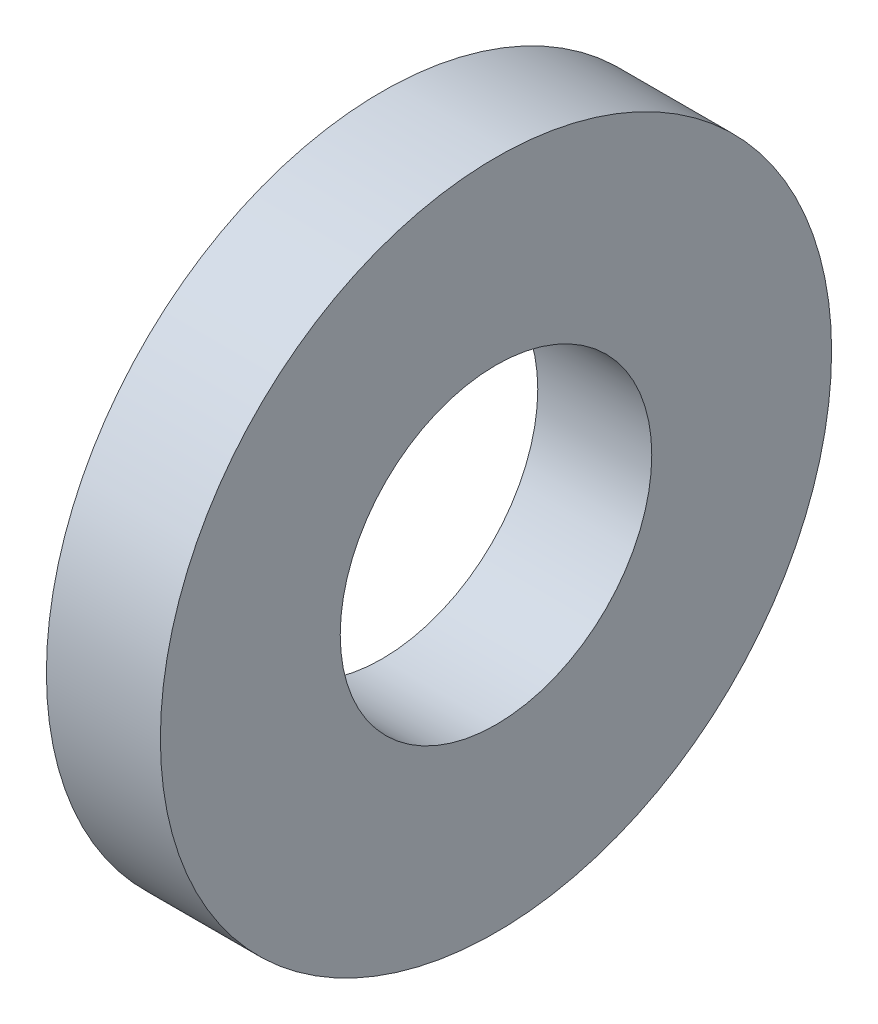
SolidWorks part; units mm, degrees
material "AISI 1020"
ref_plane "Спереди" through (0, 0, 0) normal (0, 0, 1) x (1, 0, 0)
ref_plane "Сверху" through (0, 0, 0) normal (0, 1, 0) x (1, 0, 0)
ref_plane "Справа" through (0, 0, 0) normal (1, 0, 0) x (0, 0, -1)
sketch "Эскиз1" plane through (0, 0, 0) normal (1, 0, 0) x (0, 0, -1)
  circle A1 centre (0, 0) radius 4.1 construction
  circle A2 centre (0, 0) radius 8.8333
  circle A3 centre (0, 0) radius 8.8333
  circle A4 centre (0, 0) radius 4.1
  dimension "D1" = 1
base flange "Базовая кромка1" sketch "Эскиз1" thickness 3 reverse thickness direction no parameters "D1"=0.74
sketch "Сгиб-Линии1" [suppressed] plane through (0, 0, 0) normal (0, 1, 0) x (1, 0, 0)
sketch "Граничная рамка1" [suppressed] plane through (0, 0, 0) normal (0, 1, 0) x (1, 0, 0)
sheet metal parameters "Листовой металл3" thickness 3 parameters "D1"=0.74
flat pattern "Развертка3" [suppressed]
sketch "Сгиб-Линии2" plane through (0, 0, 0) normal (0, 1, 0) x (1, 0, 0)
sketch3d "Граничная рамка2" [suppressed]
  line L0 (-8.7583, -8.9077, 0) -> (8.9077, -8.7583, 0) construction
  line L1 (-8.9077, 8.7582, 0) -> (8.7583, 8.9076, 0) construction
  line L2 (-8.7583, -8.9077, 0) -> (-8.9077, 8.7582, 0) construction
  line L3 (8.9077, -8.7583, 0) -> (8.7583, 8.9076, 0) construction
